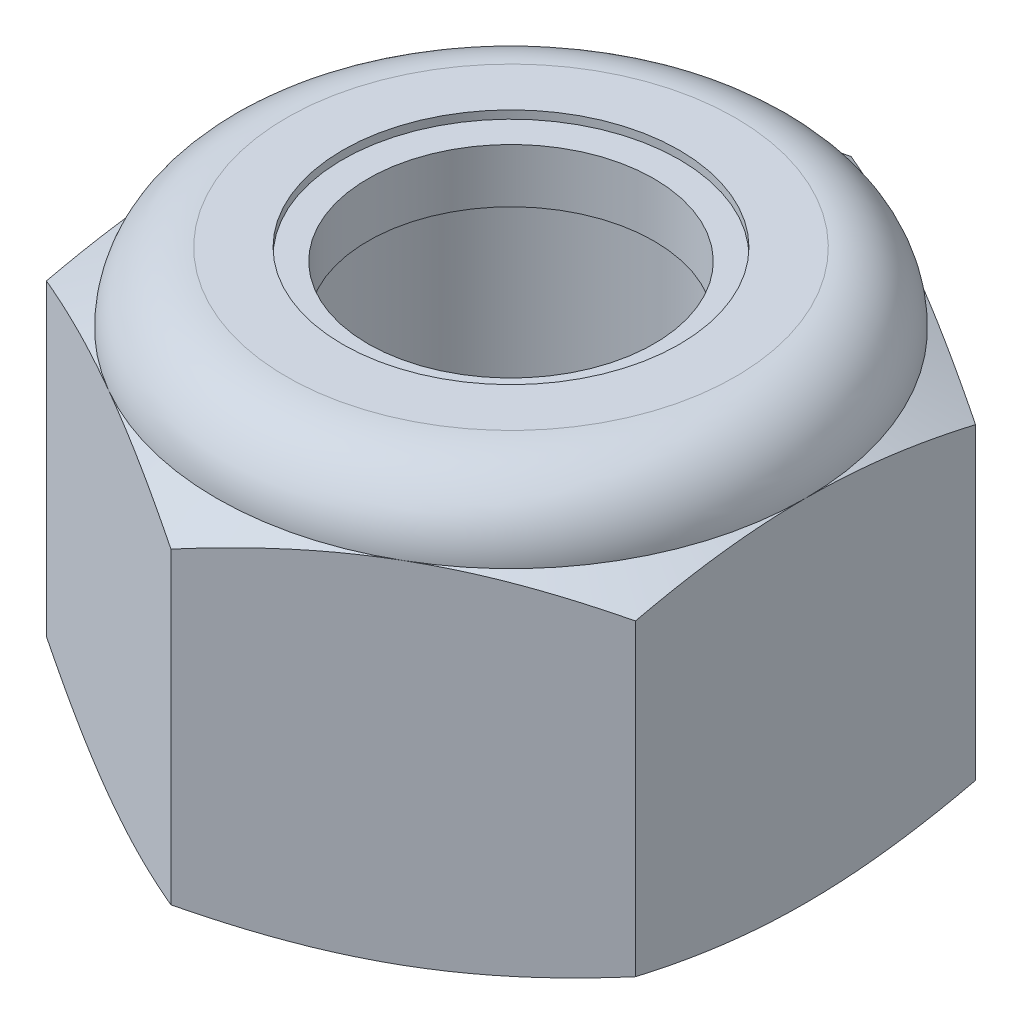
SolidWorks part; units mm, degrees
material "Cast Alloy Steel"
ref_plane "Front" through (0, 0, 0) normal (0, 0, 1) x (1, 0, 0)
ref_plane "Top" through (0, 0, 0) normal (0, 1, 0) x (1, 0, 0)
ref_plane "Right" through (0, 0, 0) normal (1, 0, 0) x (0, 0, -1)
sketch "Sketch1" plane through (0, 0, 0) normal (1, 0, 0) x (0, 0, -1)
  line L0 (0, 0) -> (0, 7.9375) construction
  line L1 (5.5562, 0) -> (-5.5562, 0) construction
  line L2 (-3.175, 7.9375) -> (3.175, 7.9375) construction
  line L3 (3.175, 7.9375) -> (3.175, 6.6675) construction
  point P9 (-3.175, 7.9375)
  point P10 (3.175, 7.9375)
  point P11 (5.5562, 0)
  dimension "Height" = 7.9375
  dimension "Hex Flats" = 11.1125
  dimension "Thread Dia" = 6.35
  dimension "Thread Pitch" = 1.27
sketch "Sketch13" plane through (0, 0, 0) normal (0, 1, 0) x (1, 0, 0)
  line L1 (0, 6.4158) -> (-5.5563, 3.2079)
  line L2 (-5.5563, 3.2079) -> (-5.5562, -3.2079)
  line L3 (-5.5562, -3.2079) -> (0, -6.4158)
  line L4 (0, -6.4158) -> (5.5563, -3.2079)
  line L5 (5.5563, -3.2079) -> (5.5563, 3.2079)
  line L6 (5.5563, 3.2079) -> (0, 6.4158)
  circle A0 centre (0, 0) radius 5.5562 construction
  circle A1 centre (0, 0) radius 3.175
  point P11 (0, -3.175)
  point P13 (0, 3.175)
extrude "Extrude1" add sketch "Sketch13" along normal up to vertex (7.9375 mm away) up to point (0, 7.9375, 0)
sketch "Sketch5" plane through (0, 0, 0) normal (1, 0, 0) x (0, 0, -1)
  line L0 (0, 0) -> (5.5562, 0)
  line L1 (5.5562, 0) -> (6.4158, 0.4008)
  line L2 (6.4158, 0.4008) -> (6.4158, 6.2138)
  line L3 (6.4158, 6.2138) -> (5.5562, 6.6146)
  line L4 (4.2333, 7.9375) -> (4.2333, 9.2075)
  line L5 (4.2333, 9.2075) -> (7.6858, 9.2075)
  line L6 (7.6858, 9.2075) -> (7.6858, -1.27)
  line L7 (7.6858, -1.27) -> (0, -1.27)
  line L8 (0, -1.27) -> (0, 0)
  line L9 (5.5562, 6.6146) -> (5.5562, 0) construction
  line L12 (6.4158, 7.9375) -> (6.4158, 0) construction
  line L13 (6.4158, 3.9688) -> (7.6858, 3.9688) construction
  line L15 (0, 0) -> (0, 9.2075) construction
  line L18 (5.5562, 0) -> (-5.5562, 0) construction
  line L19 (3.2079, 7.9375) -> (6.4158, 7.9375) construction
  line L20 (0, 9.2075) -> (4.2333, 9.2075) construction
  line L21 (3.2079, 0) -> (6.4158, 0) construction
  arc A0 (5.5562, 6.6146) -> (4.2333, 7.9375) centre (4.2333, 6.6146) ccw
  dimension "D1" = 25
  dimension "D2" = 1.27
  dimension "D4" = 1.3229
revolve "Cut-Revolve3" cut sketch "Sketch5" angle 360 about L15
sketch "Sketch4" plane through (0, 0, 0) normal (1, 0, 0) x (0, 0, -1)
  line L0 (0, 6.6146) -> (3.4925, 6.6146)
  line L1 (3.4925, 6.6146) -> (0, 4.986)
  line L3 (0, 1.6286) -> (3.4925, 0)
  line L4 (3.4925, 0) -> (0, 0)
  line L5 (0, 0) -> (0, 6.6146) construction
  line L10 (0, 0) -> (0, 7.9375) construction
  line L11 (0, 1.6286) -> (0, 0)
  line L12 (0, 6.6146) -> (0, 4.986)
  line L13 (4.8119, 6.6146) -> (0, 6.6146) construction
  dimension "D1" = 25
  dimension "D2" = 6.985
sketch "Sketch6" plane through (0, 0, 0) normal (1, 0, 0) x (0, 0, -1)
  line L0 (0, 6.6146) -> (5.4039, 6.6146)
  line L1 (4.2333, 7.7851) -> (2.1167, 7.7851)
  line L2 (0, 9.2075) -> (0, 6.6146)
  line L3 (2.1167, 9.2075) -> (0, 9.2075)
  line L4 (0, 9.2075) -> (4.2333, 9.2075) construction
  line L5 (0, 0) -> (0, 9.2075) construction
  line L6 (0, 9.2075) -> (0, 0) construction
  line L7 (2.1167, 7.7851) -> (2.1167, 9.2075)
  line L8 (4.2333, 7.9375) -> (4.2333, 7.7851) construction
  line L9 (2.1167, 7.7851) -> (0, 7.7851) construction
  line L10 (0, 7.7851) -> (0, 4.986) construction
  arc A0 (5.4039, 6.6146) -> (4.2333, 7.7851) centre (4.2333, 6.6146) ccw
  arc A1 (5.5562, 6.6146) -> (4.2333, 7.9375) centre (4.2333, 6.6146) ccw construction
  dimension "D1" = 0.1524
revolve "Cut-Revolve4" cut sketch "Sketch6" angle 360 about L6
revolve "Cut-Revolve2" cut sketch "Sketch4" angle 360 about L5
sketch "Sketch7" plane through (0, 0, 0) normal (1, 0, 0) x (0, 0, -1)
  line L0 (2.6988, 6.6908) -> (5.325, 6.6908)
  line L1 (4.2333, 7.7089) -> (2.6988, 7.7089)
  line L2 (2.6988, 7.7089) -> (2.6988, 6.6908)
  line L3 (2.6988, 6.6908) -> (0, 6.6908) construction
  line L4 (0, 6.6908) -> (0, 7.7089) construction
  line L5 (0, 7.7089) -> (2.6988, 7.7089) construction
  line L6 (2.6988, 6.6908) -> (2.6988, 6.6146) construction
  line L7 (0, 6.6146) -> (5.4039, 6.6146) construction
  line L8 (4.2333, 7.7089) -> (4.2333, 7.7851) construction
  arc A0 (5.325, 6.6908) -> (4.2333, 7.7089) centre (4.2333, 6.6146) ccw
  arc A2 (5.4039, 6.6146) -> (4.2333, 7.7851) centre (4.2333, 6.6146) ccw construction
  point P15 (2.6988, 7.7089)
  point P18 (-3.466, 7.7089)
  point P19 (3.466, 7.7089)
  dimension "D1" = 0.0762
  dimension "D2" = 5.3975
revolve "Revolve2" add sketch "Sketch7" angle 360 about L4
sketch "Sketch2" [suppressed] plane through (0, 0, 0) normal (1, 0, 0) x (0, 0, -1)
  line L0 (-3.175, 0) -> (-3.175, 6.6146) construction
  line L1 (0, 0) -> (3.175, 0)
  line L2 (0, 0) -> (0, 6.6146)
  line L3 (0, 6.6146) -> (3.175, 6.6146)
  line L4 (3.175, 0) -> (3.175, 6.6146)
  line L6 (4.8119, 6.6146) -> (5.5562, 6.6146) construction
  line L7 (0, -3.175) -> (0, 0) construction
revolve "Revolve1" [suppressed] add sketch "Sketch2" angle 360 about L7
sketch "Sketch9" [suppressed] plane through (0, 0, 0) normal (1, 0, 0) x (0, 0, -1)
  line L0 (3.3125, 7.8052) -> (3.3125, 6.5352) construction
  line L1 (3.3125, 6.5352) -> (2.2126, 7.1702) construction
  line L2 (2.2126, 7.1702) -> (3.3125, 7.8052) construction
  line L3 (2.3501, 7.2496) -> (2.3501, 7.0908) construction
  line L4 (3.175, 7.7258) -> (3.175, 6.6146) construction
  line L5 (2.2126, 7.1702) -> (2.3501, 7.1702) construction
  line L6 (3.175, 7.1702) -> (3.3125, 7.1702) construction
  line L7 (3.2437, 7.1702) -> (3.2437, 7.7655) construction
  line L8 (3.3125, 6.5352) -> (3.2437, 7.7655)
  line L9 (3.2437, 7.7655) -> (2.3501, 7.2496)
  line L10 (2.3501, 7.2496) -> (2.3501, 7.0908)
  line L11 (2.3501, 7.0908) -> (3.3125, 6.5352)
  dimension "D1" = 1.27
  dimension "D2" = 0.1588
sketch "Sketch10" [suppressed] plane through (0, 6.6146, 0) normal (0, 1, 0) x (1, 0, 0)
  circle A1 centre (0, 0) radius 3.175
  circle A2 centre (0, 0) radius 3.175
  dimension "D1" = 0
curve "Helix/Spiral1" [suppressed] pitch 1.27 height 9.2075 turns 7.25
sweep "Cut-Sweep1" [suppressed] cut profiles "Sketch9" path "Helix/Spiral1"
sketch "Sketch11" [suppressed] plane through (0, 0, 0) normal (1, 0, 0) x (0, 0, -1)
  line L0 (0, 0) -> (0, 7.9375) construction
  line L1 (5.5562, 0) -> (-5.5562, 0) construction
  line L4 (0, 7.9375) -> (0, 0) construction
  line L5 (0, 3.9688) -> (3.175, 3.9688) construction
  line L6 (0, 0) -> (3.4925, 0)
  line L7 (0, 1.6286) -> (0, 0)
  line L8 (3.4925, 0) -> (0, 1.6286)
  dimension "D1" = 6.985
  dimension "D2" = 25
revolve "Revolve3" [suppressed] add sketch "Sketch11" angle 360 about L4
sketch "Sketch12" [suppressed] plane through (0, 0, 0) normal (1, 0, 0) x (0, 0, -1)
  line L0 (3.4925, 6.6146) -> (0, 6.6146)
  line L1 (0, 6.6146) -> (0, 0)
  line L2 (0, 0) -> (3.4925, 0)
  line L3 (5.5562, 0) -> (-5.5562, 0) construction
  line L4 (3.4925, 0) -> (3.4925, 6.6146)
  line L5 (-3.4925, 0) -> (3.4925, 0) construction
revolve "Revolve4" [suppressed] add sketch "Sketch12" angle 360 about L0
combine bodies "Combine1" [suppressed] operation type subtract main body 136 bodies to subtract 133
equation "\"D4@Sketch5\" = \"Height@Sketch1\" / 6"
equation "\"D1@Sketch9\" = \"Thread Pitch@Sketch1\""
equation "\"D2@Sketch9\" = \"Thread Pitch@Sketch1\" / 8"
equation "\"D4@Helix/Spiral1\" = \"Thread Pitch@Sketch1\""
equation "\"D3@Helix/Spiral1\" = \"Thread Pitch@Sketch1\" + \"Height@Sketch1\""
equation "\"D2@Sketch4\" = \"Thread Dia@Sketch1\" * 1.1"
equation "\"D1@Sketch11\" = \"Thread Dia@Sketch1\" * 1.1"
equation "\"D2@Sketch7\" = \"Thread Dia@Sketch1\" * .85"
